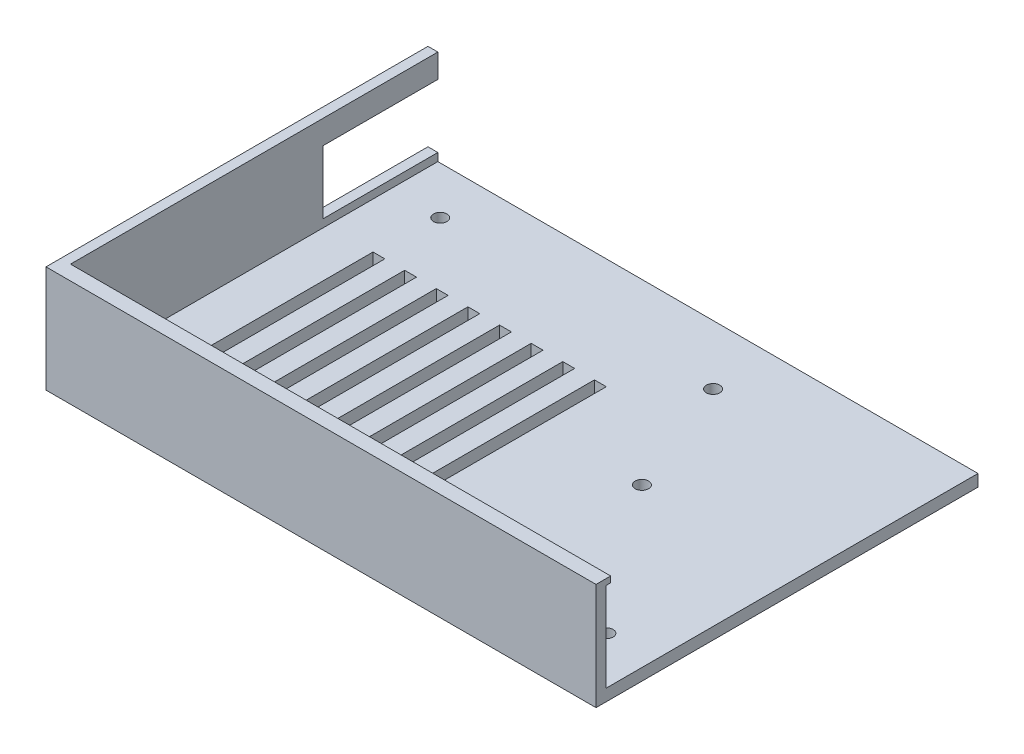
SolidWorks part; units mm, degrees
ref_plane "Front Plane" through (0, 0, 0) normal (0, 0, 1) x (1, 0, 0)
ref_plane "Top Plane" through (0, 0, 0) normal (0, 1, 0) x (1, 0, 0)
ref_plane "Right Plane" through (0, 0, 0) normal (1, 0, 0) x (0, 0, -1)
sketch "Sketch1" plane through (0, 0, 0) normal (0, 1, 0) x (1, 0, 0)
  line L1 (-139.1, -96.6) -> (139.1, -96.6)
  line L2 (-139.1, -96.6) -> (-139.1, 96.6)
  line L3 (-139.1, 96.6) -> (139.1, 96.6)
  line L4 (139.1, -96.6) -> (139.1, 96.6)
  line L5 (-139.1, -96.6) -> (139.1, 96.6) construction
  line L6 (-139.1, 96.6) -> (139.1, -96.6) construction
  dimension "D1" = 278.2
  dimension "D2" = 193.2
extrude "Shell Block" add sketch "Sketch1" along normal blind 27
ref_plane "Shell Front" through (0, 27, 0) normal (0, 1, 0) x (1, 0, 0)
sketch "Sketch2" plane through (0, 27, 0) normal (0, 1, 0) x (1, 0, 0)
  line L1 (-136.6, -92.9) -> (136.6, -92.9)
  line L2 (-136.6, -92.9) -> (-136.6, 92.9)
  line L3 (-136.6, 92.9) -> (136.6, 92.9)
  line L4 (136.6, -92.9) -> (136.6, 92.9)
  line L5 (-136.6, -92.9) -> (136.6, 92.9) construction
  line L6 (-136.6, 92.9) -> (136.6, -92.9) construction
  dimension "D1" = 273.2
  dimension "D2" = 185.8
extrude "Front Opening" cut sketch "Sketch2" against normal blind 1.5
ref_plane "Under Lip" through (0, 25.5, 0) normal (0, 1, 0) x (1, 0, 0)
sketch "Sketch3" plane through (0, 25.5, 0) normal (0, 1, 0) x (1, 0, 0)
  line L1 (-136.6, -94.1) -> (136.6, -94.1)
  line L2 (-136.6, -94.1) -> (-136.6, 94.1)
  line L3 (-136.6, 94.1) -> (136.6, 94.1)
  line L4 (136.6, -94.1) -> (136.6, 94.1)
  line L5 (-136.6, -94.1) -> (136.6, 94.1) construction
  line L6 (-136.6, 94.1) -> (136.6, -94.1) construction
  dimension "D1" = 273.2
  dimension "D2" = 188.2
extrude "Display Pocket" cut sketch "Sketch3" against normal blind 22.5
ref_plane "Back Inner" through (0, 3, 0) normal (0, 1, 0) x (1, 0, 0)
sketch "Sketch4" plane through (0, 3, 0) normal (0, 1, 0) x (1, 0, 0)
  line L1 (-69, 28) -> (-66, 28)
  line L2 (-69, 28) -> (-69, 84)
  line L3 (-69, 84) -> (-66, 84)
  line L4 (-66, 28) -> (-66, 84)
  line L6 (-69, -84) -> (-66, -84)
  line L7 (-69, -84) -> (-69, -28)
  line L8 (-69, -28) -> (-66, -28)
  line L9 (-66, -84) -> (-66, -28)
  line L11 (-77, 28) -> (-74, 28)
  line L12 (-77, 28) -> (-77, 84)
  line L13 (-77, 84) -> (-74, 84)
  line L14 (-74, 28) -> (-74, 84)
  line L16 (-77, -84) -> (-74, -84)
  line L17 (-77, -84) -> (-77, -28)
  line L18 (-77, -28) -> (-74, -28)
  line L19 (-74, -84) -> (-74, -28)
  line L21 (-85, 28) -> (-82, 28)
  line L22 (-85, 28) -> (-85, 84)
  line L23 (-85, 84) -> (-82, 84)
  line L24 (-82, 28) -> (-82, 84)
  line L26 (-85, -84) -> (-82, -84)
  line L27 (-85, -84) -> (-85, -28)
  line L28 (-85, -28) -> (-82, -28)
  line L29 (-82, -84) -> (-82, -28)
  line L31 (-93, 28) -> (-90, 28)
  line L32 (-93, 28) -> (-93, 84)
  line L33 (-93, 84) -> (-90, 84)
  line L34 (-90, 28) -> (-90, 84)
  line L36 (-93, -84) -> (-90, -84)
  line L37 (-93, -84) -> (-93, -28)
  line L38 (-93, -28) -> (-90, -28)
  line L39 (-90, -84) -> (-90, -28)
  line L41 (-101, 28) -> (-98, 28)
  line L42 (-101, 28) -> (-101, 84)
  line L43 (-101, 84) -> (-98, 84)
  line L44 (-98, 28) -> (-98, 84)
  line L46 (-101, -84) -> (-98, -84)
  line L47 (-101, -84) -> (-101, -28)
  line L48 (-101, -28) -> (-98, -28)
  line L49 (-98, -84) -> (-98, -28)
  line L51 (-109, 28) -> (-106, 28)
  line L52 (-109, 28) -> (-109, 84)
  line L53 (-109, 84) -> (-106, 84)
  line L54 (-106, 28) -> (-106, 84)
  line L56 (-109, -84) -> (-106, -84)
  line L57 (-109, -84) -> (-109, -28)
  line L58 (-109, -28) -> (-106, -28)
  line L59 (-106, -84) -> (-106, -28)
  line L61 (-117, 28) -> (-114, 28)
  line L62 (-117, 28) -> (-117, 84)
  line L63 (-117, 84) -> (-114, 84)
  line L64 (-114, 28) -> (-114, 84)
  line L66 (-117, -84) -> (-114, -84)
  line L67 (-117, -84) -> (-117, -28)
  line L68 (-117, -28) -> (-114, -28)
  line L69 (-114, -84) -> (-114, -28)
  line L71 (-125, 28) -> (-122, 28)
  line L72 (-125, 28) -> (-125, 84)
  line L73 (-125, 84) -> (-122, 84)
  line L74 (-122, 28) -> (-122, 84)
  line L76 (-125, -84) -> (-122, -84)
  line L77 (-125, -84) -> (-125, -28)
  line L78 (-125, -28) -> (-122, -28)
  line L79 (-122, -84) -> (-122, -28)
extrude "Vent Slots" cut sketch "Sketch4" against normal blind 4
sketch "Sketch5" plane through (0, 0, 0) normal (1, 0, 0) x (0, 0, -1)
  line L1 (-29, 5) -> (29, 5)
  line L2 (-29, 5) -> (-29, 21)
  line L3 (-29, 21) -> (29, 21)
  line L4 (29, 5) -> (29, 21)
extrude "Cable Exit (-X short side)" cut sketch "Sketch5" against normal blind 140.1
sketch "Sketch6" plane through (0, 3, 0) normal (0, 1, 0) x (1, 0, 0)
  circle A0 centre (-40, -45) radius 1.7
  circle A1 centre (-40, 45) radius 1.7
  circle A2 centre (40, -45) radius 1.7
  circle A3 centre (40, 45) radius 1.7
  circle A4 centre (-52, -15) radius 1.7
  circle A5 centre (-52, 15) radius 1.7
  circle A6 centre (52, -15) radius 1.7
  circle A7 centre (52, 15) radius 1.7
  circle A8 centre (-12, -82) radius 1.7
  circle A9 centre (-12, 82) radius 1.7
  circle A10 centre (12, -82) radius 1.7
  circle A11 centre (12, 82) radius 1.7
  circle A12 centre (-124, -12) radius 1.7
  circle A13 centre (-124, 12) radius 1.7
  circle A14 centre (124, -12) radius 1.7
  circle A15 centre (124, 12) radius 1.7
extrude "Bolt Holes" cut sketch "Sketch6" against normal blind 4
sketch "Sketch7" plane through (0, 0, 0) normal (0, 1, 0) x (1, 0, 0)
  line L1 (200, -200) -> (0, -200)
  line L2 (200, -200) -> (200, 200)
  line L3 (200, 200) -> (0, 200)
  line L4 (0, -200) -> (0, 200)
extrude "Keep one half (X)" cut sketch "Sketch7" against normal through all and the other way through all
sketch "Sketch8" plane through (0, 0, 0) normal (0, 1, 0) x (1, 0, 0)
  line L1 (-200, 0) -> (200, 0)
  line L2 (-200, 0) -> (-200, 200)
  line L3 (-200, 200) -> (200, 200)
  line L4 (200, 0) -> (200, 200)
extrude "Keep one quarter (Z)" cut sketch "Sketch8" against normal through all and the other way through all
equation "\"DispL\"= 272.0"
equation "\"DispW\"= 187.0"
equation "\"DispT\"= 20.0"
equation "\"Clr\"= 0.6"
equation "\"Wall\"= 2.5"
equation "\"BackT\"= 3.0"
equation "\"CableRoom\"= 4.0"
equation "\"LipW\"= 1.2"
equation "\"LipT\"= 1.5"
equation "\"CableW\"= 58.0"
equation "\"CableH\"= 16.0"
equation "\"BoltD\"= 3.4"
equation "\"ShellL\"= \"DispL\" + 2 * \"Clr\" + 2 * \"Wall\""
equation "\"ShellW\"= \"DispW\" + 2 * \"Clr\" + 2 * \"Wall\""
equation "\"ShellH\"= \"BackT\" + \"DispT\" + \"CableRoom\""
equation "\"D1@Sketch1\" = \"ShellL\""
equation "\"D2@Sketch1\" = \"ShellW\""
equation "\"D1@Shell Block\" = \"ShellH\""
equation "\"D1@Shell Front\" = \"ShellH\""
equation "\"D1@Sketch2\" = \"DispL\" + 2 * \"Clr\""
equation "\"D2@Sketch2\" = \"DispW\" + 2 * \"Clr\" - 2 * \"LipW\""
equation "\"D1@Front Opening\" = \"LipT\""
equation "\"D1@Under Lip\" = \"ShellH\" - \"LipT\""
equation "\"D1@Sketch3\" = \"DispL\" + 2 * \"Clr\""
equation "\"D2@Sketch3\" = \"DispW\" + 2 * \"Clr\""
equation "\"D1@Display Pocket\" = \"ShellH\" - \"LipT\" - \"BackT\""
equation "\"D1@Back Inner\" = \"BackT\""
